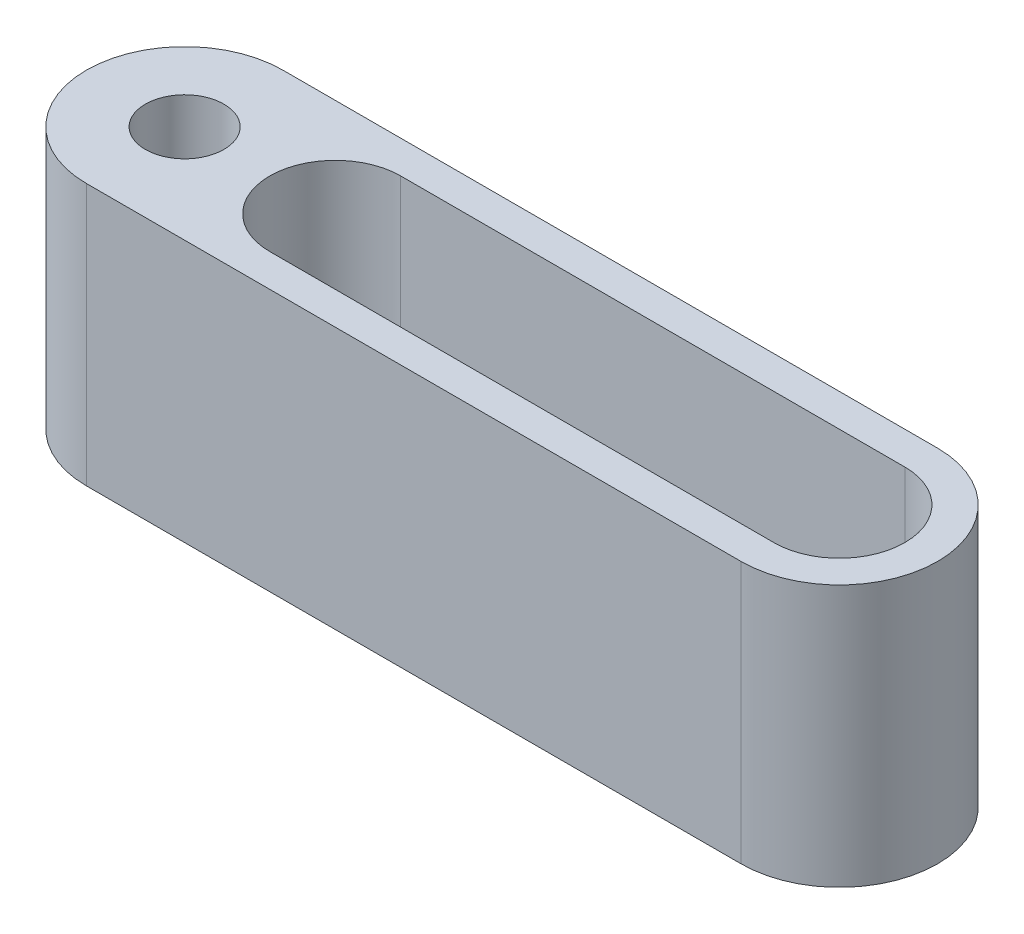
SolidWorks part; units mm, degrees
note: The reader was unsure of these and kept them because the rebuilt part matched: shared geometry of "Sketch1<2>".
ref_plane "Front Plane" through (0, 0, 0) normal (0, 0, 1) x (1, 0, 0)
ref_plane "Top Plane" through (0, 0, 0) normal (0, 1, 0) x (1, 0, 0)
ref_plane "Right Plane" through (0, 0, 0) normal (1, 0, 0) x (0, 0, -1)
sketch "Sketch1" plane through (0, 0, 0) normal (0, 1, 0) x (1, 0, 0)
  line L0 (0, -15) -> (100, -15)
  line L1 (-15, 0) -> (112.6439, 0) construction
  line L2 (0, 15) -> (100, 15)
  line L3 (23, 10) -> (100, 10)
  line L4 (23, -10) -> (100, -10)
  circle A0 centre (0, 0) radius 6
  arc A1 (0, 15) -> (0, -15) centre (0, 0) ccw
  arc A2 (100, 15) -> (100, -15) centre (100, 0) cw
  arc A3 (23, 10) -> (23, -10) centre (23, 0) ccw
  arc A4 (100, -10) -> (100, 10) centre (100, 0) ccw
  dimension "D1" = 12
extrude "Boss-Extrude1" add sketch "Sketch1" along normal blind 40
extrude "Boss-Extrude2" add sketch "Sketch1<2>" along normal blind 4 contours A3 L1 A4 L3 | L1 A3 L4 A4 | A0 L1 | L1 A0
sketch "Sketch1<2>" plane through (0, 0, 0) normal (0, 1, 0) x (1, 0, 0) same geometry as "Sketch1"
